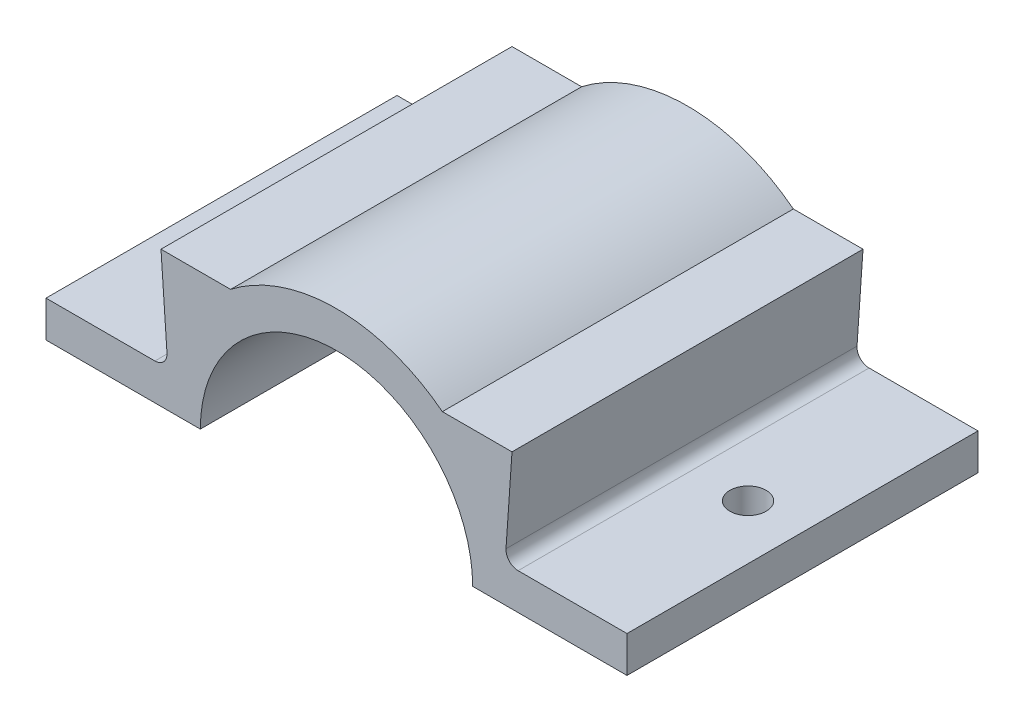
SolidWorks part; units mm, degrees
ref_plane "Front Plane" through (0, 0, 0) normal (0, 0, 1) x (1, 0, 0)
ref_plane "Top Plane" through (0, 0, 0) normal (0, 1, 0) x (1, 0, 0)
ref_plane "Right Plane" through (0, 0, 0) normal (1, 0, 0) x (0, 0, -1)
sketch "Sketch1" plane through (0, 0, 0) normal (0, 0, 1) x (1, 0, 0)
  line L0 (-11.25, -7.125) -> (-20, -7.125)
  line L1 (11.25, -7.125) -> (20, -7.125)
  line L2 (15.002, -4.125) -> (20, -4.125)
  line L3 (-15.002, -4.125) -> (-20, -4.125)
  line L4 (-14.0044, -3.0561) -> (-14.5, 4.125)
  line L5 (-14.5, 4.125) -> (-8.7464, 4.125)
  line L6 (14.5, 4.125) -> (14.0044, -3.0561)
  line L7 (8.7464, 4.125) -> (14.5, 4.125)
  line L8 (-24, -7.125) -> (-20, -7.125)
  line L9 (-24, -7.125) -> (-24, -4.125)
  line L10 (-24, -4.125) -> (-20, -4.125)
  line L11 (24, -7.125) -> (20, -7.125)
  line L12 (24, -7.125) -> (24, -4.125)
  line L13 (24, -4.125) -> (20, -4.125)
  arc A0 (11.25, -7.125) -> (-11.25, -7.125) centre (0, -7.125) ccw
  arc A1 (-14.0044, -3.0561) -> (-15.002, -4.125) centre (-15.002, -3.125) cw
  arc A2 (15.002, -4.125) -> (14.0044, -3.0561) centre (15.002, -3.125) cw
  arc A3 (8.7464, 4.125) -> (-8.7464, 4.125) centre (0, -7.125) ccw
  point P18 (24, -7.125)
  point P19 (-24, -7.125)
  dimension "D2" = 1
  dimension "D1" = 20
  dimension "D3" = 4
  dimension "D4" = 4
extrude "Boss-Extrude1" add sketch "Sketch1" along normal blind 14.5 and the other way blind 14.5
sketch "Sketch2" plane through (0, -4.125, 0) normal (0, 1, 0) x (1, 0, 0)
  circle A0 centre (-19.501, 0) radius 1.5
  circle A1 centre (19.501, 0) radius 1.5
extrude "Cut-Extrude1" cut sketch "Sketch2" against normal blind 14.5
equation "\"`14.5\"=14.5"
